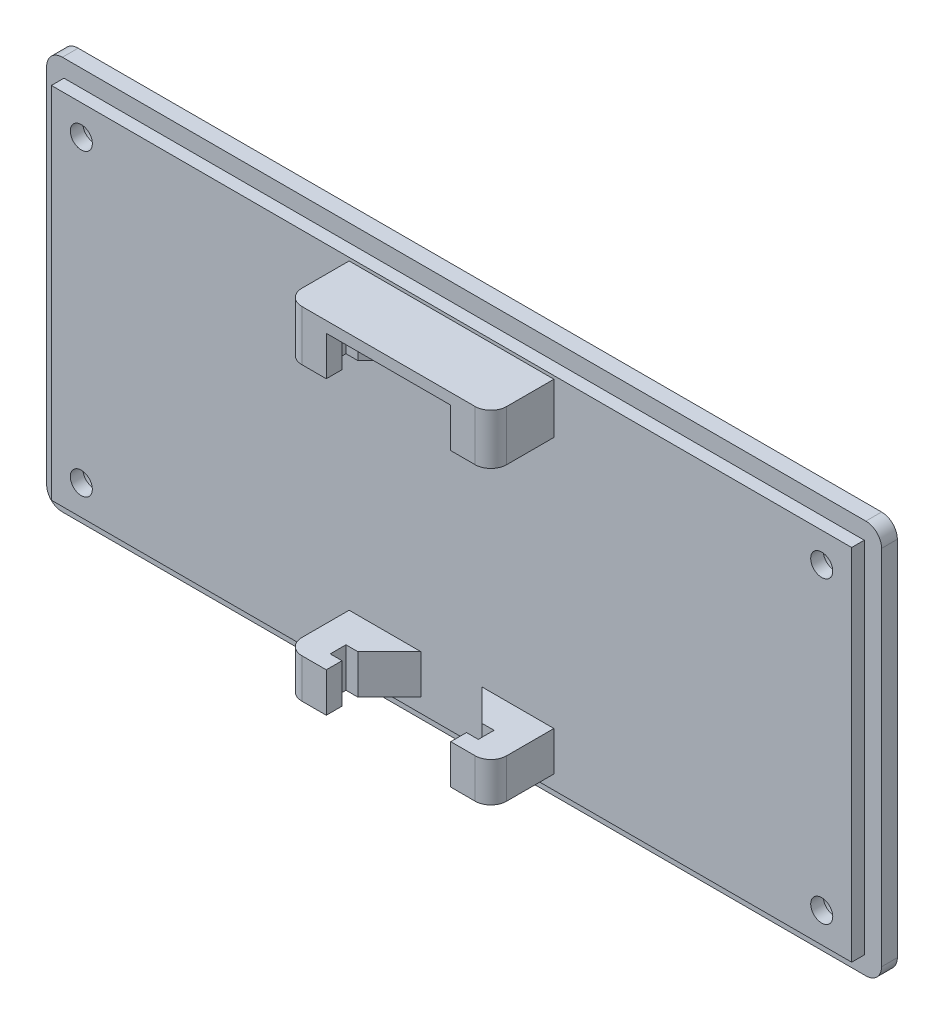
SolidWorks part; units mm, degrees
material "ABS"
ref_plane "Спереди" through (0, 0, 0) normal (0, 0, 1) x (1, 0, 0)
ref_plane "Сверху" through (0, 0, 0) normal (0, 1, 0) x (1, 0, 0)
ref_plane "Справа" through (0, 0, 0) normal (1, 0, 0) x (0, 0, -1)
sketch "Эскиз1" plane through (0, 0, 0) normal (0, 0, 1) x (1, 0, 0)
  line L1 (-53, -25) -> (53, -25)
  line L2 (-53, -25) -> (-53, 25)
  line L3 (-53, 25) -> (53, 25)
  line L4 (53, -25) -> (53, 25)
  line L5 (-53, -25) -> (53, 25) construction
  line L6 (-53, 25) -> (53, -25) construction
  point P0 (0, 0)
  dimension "D1" = 106
  dimension "D2" = 50
extrude "Body" add sketch "Эскиз1" along normal blind 2
sketch "Эскиз2" plane through (0, 0, 2) normal (0, 0, 1) x (1, 0, 0)
  line L0 (-53, 25) -> (-53, -25) construction
  line L1 (-50.8, -22.8) -> (50.8, -22.8)
  line L2 (-50.8, -22.8) -> (-50.8, 22.8)
  line L3 (-50.8, 22.8) -> (50.8, 22.8)
  line L4 (50.8, -22.8) -> (50.8, 22.8)
  line L5 (-50.8, -22.8) -> (50.8, 22.8) construction
  line L6 (-50.8, 22.8) -> (50.8, -22.8) construction
  line L7 (53, 25) -> (-53, 25) construction
  point P0 (0, 0)
  dimension "D1" = 2.2
  dimension "D2" = 2.2
extrude "InternalBody" add sketch "Эскиз2" along normal blind 1.6
sketch "Эскиз3" plane through (0, 0, 0) normal (0, 0, -1) x (-1, 0, 0)
  line L0 (53, -25) -> (-53, -25) construction
  line L1 (51, -23) -> (43, -23) construction
  line L2 (51, -23) -> (51, -15) construction
  line L3 (51, -15) -> (43, -15) construction
  line L4 (43, -23) -> (43, -15) construction
  line L5 (51, -23) -> (43, -15) construction
  line L6 (51, -15) -> (43, -23) construction
  line L7 (53, 25) -> (53, -25) construction
  circle A0 centre (47, -19) radius 1.4
  circle A1 centre (47, -19) radius 2.5
  point P0 (47, -19)
  dimension "D4" = 2.8
  dimension "D5" = 5
  dimension "D1" = 2
  dimension "D2" = 2
  dimension "D3" = 8
extrude "HoleScrew" cut sketch "Эскиз3" against normal through all contours A0 region at (-47, -19, 0)
extrude "TopScrewPlace" cut sketch "Эскиз3<3>" against normal blind 2 contours A1 A0 region at (-44.5707, -19, 0)
sketch "Эскиз3<3>" plane through (0, 0, 0) normal (0, 0, -1) x (-1, 0, 0) same geometry as "Эскиз3"
mirror "ScrewMrror1" about plane through (0, 0, 0) normal (0, 1, 0) of "TopScrewPlace", "HoleScrew"
mirror "ScrewMirror2" about plane through (0, 0, 0) normal (1, 0, 0) of "ScrewMrror1", "TopScrewPlace"
fillet "Corners" radius 2 4 edges at (-53, -25, 1) (53, -25, 1) (53, 25, 1) (-53, 25, 1)
sketch "Эскиз4" plane through (0, 0, 3.6) normal (0, 0, 1) x (1, 0, 0)
  line L1 (13, 22.4) -> (-13, 22.4)
  line L2 (13, 22.4) -> (13, 21)
  line L3 (13, 21) -> (-13, 21)
  line L4 (-13, 22.4) -> (-13, 21)
  line L5 (13, 22.4) -> (-13, 21) construction
  line L6 (13, 21) -> (-13, 22.4) construction
  line L7 (50.8, 22.8) -> (-50.8, 22.8) construction
  point P0 (0, 21.7)
  point P5 (0, 16.8566)
  point P7 (0, 0)
  dimension "D1" = 0.4
  dimension "D2" = 1.4
  dimension "D3" = 26
extrude "ArduinoNanoStops" add sketch "Эскиз4" along normal blind 8
sketch "Эскиз5" plane through (0, 21, 0) normal (0, -1, 0) x (1, 0, 0)
  line L0 (-7.9, 11.6) -> (-7.9, 9.6)
  line L1 (-13, 11.6) -> (13, 11.6) construction
  line L2 (-7.9, 9.6) -> (-9.4, 9.6)
  line L3 (-9.4, 9.6) -> (-9.4, 7.6)
  line L4 (-9.4, 7.6) -> (-7.9, 7.6)
  line L5 (-7.9, 7.6) -> (-7.9, 3.6)
  line L6 (-13, 3.6) -> (13, 3.6) construction
  line L7 (-7.9, 3.6) -> (-13, 3.6)
  line L8 (-13, 3.6) -> (-13, 11.6)
  line L9 (-13, 11.6) -> (-7.9, 11.6)
  line L10 (0, 0) -> (0, 19.1007) construction
  line L11 (7.9, 11.6) -> (7.9, 9.6)
  line L12 (7.9, 9.6) -> (9.4, 9.6)
  line L13 (9.4, 9.6) -> (9.4, 7.6)
  line L14 (9.4, 7.6) -> (7.9, 7.6)
  line L15 (7.9, 7.6) -> (7.9, 3.6)
  line L16 (7.9, 3.6) -> (13, 3.6)
  line L17 (13, 3.6) -> (13, 11.6)
  line L18 (13, 11.6) -> (7.9, 11.6)
  dimension "D1" = 15.8
  dimension "D2" = 18.8
  dimension "D3" = 2
  dimension "D4" = 2
extrude "ArduinoNanoHolder1" add sketch "Эскиз5" along normal blind 5
pattern_linear "Линейный массив1" count 2 spacing 37 along (0, -1, 0) of "ArduinoNanoHolder1"
chamfer "Фаска1" distance 4 angle 45 4 edges at (7.9, 18.5, 3.6) (7.9, -18.5, 3.6) (-7.9, -18.5, 3.6) (-7.9, 18.5, 3.6)
fillet "Скругление1" radius 2 4 edges at (13, 19.2, 11.6) (13, -18.5, 11.6) (-13, -18.5, 11.6) (-13, 19.2, 11.6)
equation "\"D3@Эскиз4\"=18+4*2"
equation "\"D1@Эскиз5\"=18+0.4*2-1.5*2"
